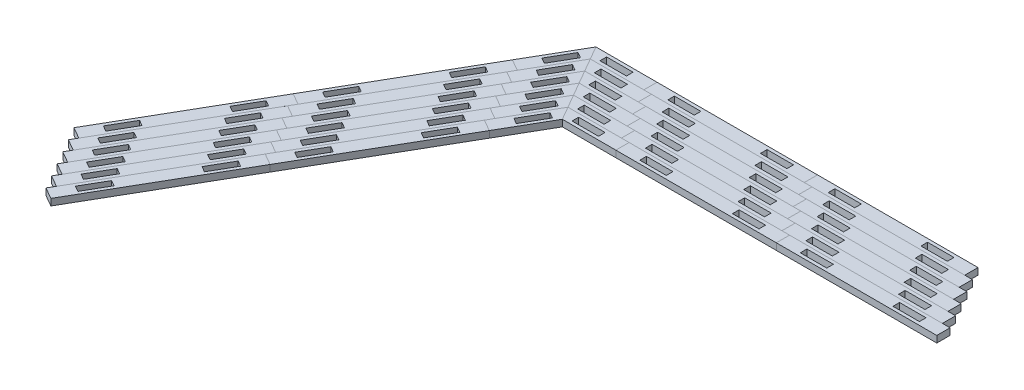
SolidWorks part; units mm, degrees
material "Cedar"
ref_plane "Front Plane" through (0, 0, 0) normal (0, 0, 1) x (1, 0, 0)
ref_plane "Top Plane" through (0, 0, 0) normal (0, 1, 0) x (1, 0, 0)
ref_plane "Right Plane" through (0, 0, 0) normal (1, 0, 0) x (0, 0, -1)
sketch "Sketch1" plane through (0, 0, 0) normal (0, 1, 0) x (1, 0, 0)
  line L0 (-76.9897, 0) -> (76.9897, 0) construction
  line L1 (-76.9897, 0) -> (0, -44.45)
  line L2 (0, -44.45) -> (76.9897, 0)
  line L3 (76.9897, 0) -> (76.9897, 88.9)
  line L4 (76.9897, 88.9) -> (0, 133.35)
  line L5 (0, 133.35) -> (-76.9897, 88.9)
  line L6 (-76.9897, 88.9) -> (-76.9897, 0)
  line L7 (0, -44.45) -> (0, 44.45) construction
  circle A0 centre (0, 44.45) radius 76.9897 construction
  point P9 (0, 0)
  dimension "D1" = 88.9
extrude "Boss-Extrude1" add sketch "Sketch1" against normal blind 6.35
sketch "Sketch2" plane through (0, 0, 0) normal (0, 1, 0) x (1, 0, 0)
  line L0 (-76.9897, 44.45) -> (76.9897, 44.45) construction
  line L1 (-76.9897, 88.9) -> (-76.9897, 0) construction
  line L2 (76.9897, 0) -> (76.9897, 88.9) construction
  point P2 (0, 44.45)
ref_axis "Axis1" through (0, 0, -44.45) along (0, 1, 0)
sketch "Sketch10" plane through (0, 0, 0) normal (0, 1, 0) x (1, 0, 0)
  line L0 (0, -44.45) -> (-21.997, -31.75) construction
  line L1 (-21.997, -31.75) -> (-13.3228, -29.4257)
  line L2 (-13.3228, -29.4257) -> (-35.3198, -16.7257)
  line L3 (-35.3198, -16.7257) -> (-38.4948, -22.225)
  line L4 (-21.997, -31.75) -> (-38.4948, -22.225)
  line L5 (-76.9897, 0) -> (0, -44.45) construction
  dimension "D1" = 45
  dimension "D2" = 6.35
extrude "Cut-Extrude4" cut sketch "Sketch10" against normal through all
sketch "Sketch11" plane through (0, 0, 0) normal (0, 1, 0) x (1, 0, 0)
  line L0 (-38.4948, -22.225) -> (-76.9897, 0) construction
  line L1 (-38.4948, -22.225) -> (-41.6698, -27.7243)
  line L2 (-41.6698, -27.7243) -> (-63.6669, -15.0243)
  line L3 (-63.6669, -15.0243) -> (-54.9926, -12.7)
  line L4 (-54.9926, -12.7) -> (-38.4948, -22.225)
  line L5 (-54.9926, -12.7) -> (-76.9897, 0) construction
  line L6 (-54.9926, -12.7) -> (-76.9897, 0) construction
  line L7 (-76.9897, 0) -> (-38.4948, -22.225) construction
  line L8 (-76.9897, 88.9) -> (-76.9897, 0) construction
  dimension "D1" = 45
  dimension "D2" = 6.35
extrude "Boss-Extrude4" add sketch "Sketch11" against normal blind 6.35
pattern_circular "CirPattern1" count 2 every 60 about axis through (0, 0, -44.45) along (0, 1, 0) of "Cut-Extrude4", "Boss-Extrude4"
sketch "Sketch12" plane through (0, 0, 0) normal (0, 1, 0) x (1, 0, 0)
  line L0 (-76.9897, 12.7) -> (76.9897, 12.7)
  line L1 (-76.9897, 88.9) -> (-76.9897, 0) construction
  line L2 (76.9897, 0) -> (76.9897, 88.9) construction
  line L3 (76.9897, 12.7) -> (76.9897, 133.35)
  line L4 (76.9897, 133.35) -> (-76.9897, 133.35)
  line L5 (-76.9897, 133.35) -> (-76.9897, 12.7)
  line L6 (0, 0) -> (0, 12.7) construction
  dimension "D1" = 12.7
extrude "Cut-Extrude5" cut sketch "Sketch12" against normal through all
sketch "Sketch13" plane through (0, 0, 0) normal (0, 1, 0) x (1, 0, 0)
  line L0 (0, 0) -> (0, 12.7) construction
  line L1 (-76.9897, 12.7) -> (76.9897, 12.7) construction
  line L2 (-44.45, 6.35) -> (44.45, 6.35) construction
  line L4 (-57.15, 9.525) -> (-31.75, 9.525)
  line L5 (-57.15, 9.525) -> (-57.15, 3.175)
  line L6 (-57.15, 3.175) -> (-31.75, 3.175)
  line L7 (-31.75, 9.525) -> (-31.75, 3.175)
  line L8 (-57.15, 9.525) -> (-31.75, 3.175) construction
  line L9 (-57.15, 3.175) -> (-31.75, 9.525) construction
  line L10 (31.75, 9.525) -> (57.15, 9.525)
  line L11 (31.75, 9.525) -> (31.75, 3.175)
  line L12 (31.75, 3.175) -> (57.15, 3.175)
  line L13 (57.15, 9.525) -> (57.15, 3.175)
  line L14 (31.75, 9.525) -> (57.15, 3.175) construction
  line L15 (31.75, 3.175) -> (57.15, 9.525) construction
  point P7 (0, 6.35)
  point P8 (0, 6.35)
  dimension "D1" = 6.35
  dimension "D2" = 25.4
  dimension "D3" = 6.35
  dimension "D4" = 25.4
  dimension "D5" = 88.9
extrude "Cut-Extrude6" cut sketch "Sketch13" against normal through all
pattern_linear "LPattern1" count 5 spacing 153.9793 along (1, 0, 0) count 2 spacing 153.9793 along (-1, 0, 0) pattern seed only yes of bodies 136 131
sketch "Sketch14" plane through (0, 0, 0) normal (0, 1, 0) x (1, 0, 0)
  line L0 (615.9173, -44.45) -> (615.9173, 12.7)
  line L1 (538.9276, 12.7) -> (692.9069, 12.7) construction
  line L2 (615.9173, 12.7) -> (692.9069, 12.7)
  line L3 (692.9069, 12.7) -> (692.9069, -44.45)
  line L4 (692.9069, -44.45) -> (615.9173, -44.45)
  line L5 (-153.9793, -44.45) -> (-153.9793, 12.7)
  line L6 (-230.969, 12.7) -> (-76.9897, 12.7) construction
  line L7 (-153.9793, 12.7) -> (-230.969, 12.7)
  line L8 (-230.969, 12.7) -> (-230.969, -44.45)
  line L9 (-230.969, -44.45) -> (-153.9793, -44.45)
  line L10 (580.5974, -16.7257) -> (597.5864, 12.7)
  line L11 (597.5864, 12.7) -> (615.9173, 12.7)
  line L12 (580.5974, -16.7257) -> (574.2474, -27.7243)
  line L13 (574.2474, -27.7243) -> (615.9173, -44.45)
  line L14 (-112.3095, -27.7243) -> (-135.6484, 12.7)
  line L15 (-135.6484, 12.7) -> (-153.9793, 12.7)
  line L16 (-112.3095, -27.7243) -> (-134.3065, -40.4243)
  line L17 (-134.3065, -40.4243) -> (-153.9793, -44.45)
  line L18 (-118.6595, -16.7257) -> (-112.3095, -27.7243) construction
  line M5 (673.0673, 9.525) -> (673.0673, 3.175)
  line M6 (673.0673, 3.175) -> (647.6673, 3.175)
  line M7 (647.6673, 3.175) -> (647.6673, 9.525)
  line M8 (647.6673, 9.525) -> (673.0673, 9.525)
  line M13 (692.9069, 12.7) -> (538.9276, 12.7)
  line M19 (580.5974, -16.7257) -> (602.5945, -29.4257)
  line M20 (602.5945, -29.4257) -> (593.9202, -31.75)
  line M21 (593.9202, -31.75) -> (615.9173, -44.45)
  line M22 (615.9173, -44.45) -> (637.9143, -31.75)
  line M23 (637.9143, -31.75) -> (635.5901, -40.4243)
  line M24 (635.5901, -40.4243) -> (657.5871, -27.7243)
  line M25 (657.5871, -27.7243) -> (651.2371, -16.7257)
  line M26 (651.2371, -16.7257) -> (673.2341, -4.0257)
  line M27 (673.2341, -4.0257) -> (670.9099, -12.7)
  line M28 (670.9099, -12.7) -> (692.9069, 0)
  line M29 (692.9069, 0) -> (692.9069, 12.7)
extrude "Cut-Extrude7" cut sketch "Sketch14" against normal through all contours L17 L16 L14 L15 L5 | L10 L0 M19 M20 M21 M13 | L0 M22 M23 M24 M25 M26 M27 M28 M29 M13 M8 M5 M6 M7 | L8 L9 L5 L7 region at (603.1355, 0, 12.4572) region at (644.4492, 0, 8.9256) region at (-192.4741, 0, 15.875) region at (-138.3884, 0, 16.3957)
sketch "Sketch15" plane through (0, 0, 0) normal (0, 1, 0) x (1, 0, 0)
  line L0 (-156.381, 0) -> (618.319, 0)
  line L3 (-156.381, 0) -> (-156.381, -63.5)
  line L4 (-156.381, -63.5) -> (618.319, -63.5)
  line L5 (618.319, -63.5) -> (618.319, 0)
  line L6 (230.969, 0) -> (230.969, 12.7)
  line L7 (230.969, 12.7) -> (618.319, 12.7)
  line L8 (618.319, 12.7) -> (618.319, 0)
  point P4 (230.969, 0)
  line M15 (-76.9897, 0) -> (-54.9926, -12.7)
  line M16 (-54.9926, -12.7) -> (-63.6669, -15.0243)
  line M17 (-63.6669, -15.0243) -> (-41.6698, -27.7243)
  line M18 (-41.6698, -27.7243) -> (-35.3198, -16.7257)
  line M19 (-35.3198, -16.7257) -> (-13.3228, -29.4257)
  line M20 (-13.3228, -29.4257) -> (-21.997, -31.75)
  line M21 (-21.997, -31.75) -> (0, -44.45)
  line M22 (0, -44.45) -> (21.997, -31.75)
  line M23 (21.997, -31.75) -> (19.6728, -40.4243)
  line M24 (19.6728, -40.4243) -> (41.6698, -27.7243)
  line M25 (41.6698, -27.7243) -> (35.3198, -16.7257)
  line M26 (35.3198, -16.7257) -> (57.3169, -4.0257)
  line M27 (57.3169, -4.0257) -> (54.9926, -12.7)
  line M28 (54.9926, -12.7) -> (76.9897, 0)
  dimension "D1" = 63.5
  dimension "D2" = 774.7
extrude "Cut-Extrude8" cut sketch "Sketch15" against normal through all contours L8 L7 L6 L0 | L4 L5 L0 L3 M28 M27 M26 M25 M24 M23 M22 M21 M20 M19 M18 M17 M16 M15 | L0 M15 M16 M17 M18 M19 M20 M21 M22 M23 M24 M25 M26 M27 M28 | L5 L0 L3 L4 region at (248.3574, 0, 32.9805) region at (-1.5983, 0, 15.2918) region at (424.644, 0, -6.35)
mirror "Mirror1" about plane through (-96.2371, -6.35, 55.5625) normal (0.866, 0, -0.5) of bodies 151 149 146
pattern_linear "LPattern2" count 6 spacing 14.6647 along (0.5, 0, 0.866) of bodies 154 151 146 149 152 153
